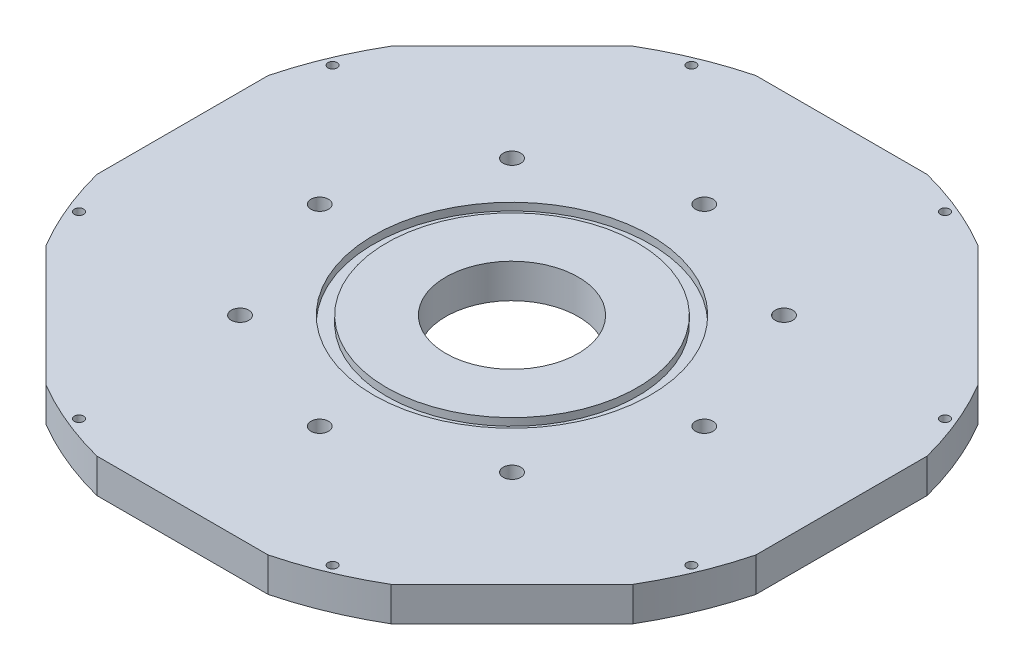
SolidWorks part; units mm, degrees
other "Markup1"
sketch "Sketch46" plane through (-122.3, 0, 122.3) normal (-0.1263, -0.9546, 0.2699) x (-0.172, -0.2469, -0.9537)
material "6061-T6 (SS)"
ref_plane "Front Plane" through (0, 0, 0) normal (0, 0, 1) x (1, 0, 0)
ref_plane "Top Plane" through (0, 0, 0) normal (0, 1, 0) x (1, 0, 0)
ref_plane "Right Plane" through (0, 0, 0) normal (1, 0, 0) x (0, 0, -1)
sketch "Sketch1" plane through (0, 0, 0) normal (0, 1, 0) x (1, 0, 0)
  line L1 (-50.6583, 122.3) -> (-122.3, 50.6583)
  line L2 (-122.3, 50.6583) -> (-122.3, -50.6583)
  line L3 (-122.3, -50.6583) -> (-50.6583, -122.3)
  line L4 (-50.6583, -122.3) -> (50.6583, -122.3)
  line L5 (50.6583, -122.3) -> (122.3, -50.6583)
  line L6 (122.3, -50.6583) -> (122.3, 50.6583)
  line L7 (122.3, 50.6583) -> (50.6583, 122.3)
  line L8 (50.6583, 122.3) -> (-50.6583, 122.3)
  circle A0 centre (0, 0) radius 122.3 construction
  circle A1 centre (0, 0) radius 126.365
  dimension "D2" = 252.73
  dimension "D1" = 244.6
extrude "Boss-Extrude1" add sketch "Sketch1" along normal blind 12.7 contours L4 A1 L5 L6 L7 L8 L1 L2 L3 region at (0, 0, 0)
sketch "Sketch3" plane through (0, 12.7, 0) normal (0, 1, 0) x (1, 0, 0)
  circle A0 centre (0, 0) radius 24.5745
  dimension "D1" = 49.149
extrude "Cut-Extrude1" cut sketch "Sketch3" against normal through all contours A0
sketch "Sketch5" plane through (0, 12.7, 0) normal (0, 1, 0) x (1, 0, 0)
  circle A0 centre (0, 0) radius 46.5455
  circle A1 centre (0, 0) radius 51.3715
  dimension "D1" = 93.091
  dimension "D2" = 102.743
extrude "Cut-Extrude2" cut sketch "Sketch5" against normal blind 2.794
sketch "Sketch19" plane through (0, 12.7, 0) normal (0, 1, 0) x (1, 0, 0)
  line L5 (-63.9978, 108.9605) -> (-31.7934, 122.3) construction
  line L6 (-47.8956, 115.6303) -> (-43.6974, 105.4949) construction
  circle A4 centre (0, 0) radius 122.9995
  circle A5 centre (-47.0699, 113.6367) radius 2.2479
  dimension "D1" = 4.4958
  dimension "D3" = 245.999
sketch "Sketch21" plane through (0, 12.7, 0) normal (0, 1, 0) x (1, 0, 0)
  point P0 (-71.374, 0)
  dimension "D1" = 71.374
hole_wizard "5/16-18 Tapped Hole1" positions "Sketch22" profile "Sketch23" tap size "5/16-18" standard "ANSI Inch"
sketch "Sketch22" plane through (0, 12.7, 0) normal (0, 1, 0) x (1, 0, 0)
  point P0 (-71.374, 0)
sketch "Sketch23" plane through (-71.374, 12.7, 0) normal (1, 0, 0) x (0, 0, 1)
  line L0 (0, 0) -> (0, 8.3111)
  line L1 (0, 8.3111) -> (3.2639, 6.35)
  line L2 (3.2639, 6.35) -> (3.2639, 0)
  line L5 (3.2639, 0) -> (0, 0)
  line L10 (0, 8.3111) -> (-3.2639, 6.35) construction
  line L11 (0, -6.35) -> (0, 107.95) construction
  dimension "Tap Drill Dia." = 6.5278
  dimension "Tap Drill Depth" = 6.35
  dimension "Drill Angle" = 118
cosmetic thread "Hole Thread2" parameters "D1"=6.35, "D2"=7.9375
sketch "Sketch33" [suppressed] plane through (0, 19.05, 0) normal (0, 1, 0) x (1, 0, 0)
  circle A0 centre (-71.374, 0) radius 3.9687
  dimension "D1" = 7.9375
sketch "Sketch37" plane through (0, 0, 0) normal (0, -1, 0) x (1, 0, 0)
  circle A0 centre (0, 0) radius 119.0625
  circle A1 centre (0, 0) radius 115.2525
  dimension "D1" = 238.125
  dimension "D2" = 230.505
extrude "Cut-Extrude7" cut sketch "Sketch37" against normal blind 2.667
pattern_circular "CirPattern4" count 8 over 360 about axis through (0, 0, 0) along (0, 1, 0) of "5/16-18 Tapped Hole1" reverse direction yes
cosmetic thread "Hole Thread3" parameters "D1"=6.35, "D2"=7.9375
cosmetic thread "Hole Thread4" parameters "D1"=6.35, "D2"=7.9375
cosmetic thread "Hole Thread5" parameters "D1"=6.35, "D2"=7.9375
cosmetic thread "Hole Thread6" parameters "D1"=6.35, "D2"=7.9375
cosmetic thread "Hole Thread7" parameters "D1"=6.35, "D2"=7.9375
cosmetic thread "Hole Thread8" parameters "D1"=6.35, "D2"=7.9375
cosmetic thread "Hole Thread9" parameters "D1"=6.35, "D2"=7.9375
hole_wizard "#8-32 Tapped Hole1" positions "Sketch47" profile "Sketch49" tap size "#8-32" standard "ANSI Inch" end condition through all
sketch "Sketch47" plane through (0, 12.7, 0) normal (0, 1, 0) x (1, 0, 0)
  point P0 (-47.0699, 113.6367)
sketch "Sketch49" plane through (-47.0699, 12.7, -113.6367) normal (1, 0, 0) x (0, 0, 1)
  line L0 (0, 0) -> (0, 12.7)
  line L1 (0, 12.7) -> (1.7272, 12.7)
  line L2 (1.7272, 12.7) -> (1.7272, 0)
  line L5 (1.7272, 0) -> (0, 0)
  line L11 (0, -6.35) -> (0, 107.95) construction
  dimension "Thru Tap Drill Dia." = 3.4544
  dimension "Thru Tap Drill Depth" = 12.7
cosmetic thread "Hole Thread10" parameters "D2"=4.1656
pattern_circular "CirPattern5" count 8 over 360 about axis through (0, 0, 0) along (0, 1, 0) of "#8-32 Tapped Hole1"
cosmetic thread "Hole Thread11" parameters "D2"=4.1656
cosmetic thread "Hole Thread12" parameters "D2"=4.1656
cosmetic thread "Hole Thread13" parameters "D2"=4.1656
cosmetic thread "Hole Thread14" parameters "D2"=4.1656
cosmetic thread "Hole Thread15" parameters "D2"=4.1656
cosmetic thread "Hole Thread16" parameters "D2"=4.1656
cosmetic thread "Hole Thread17" parameters "D2"=4.1656
